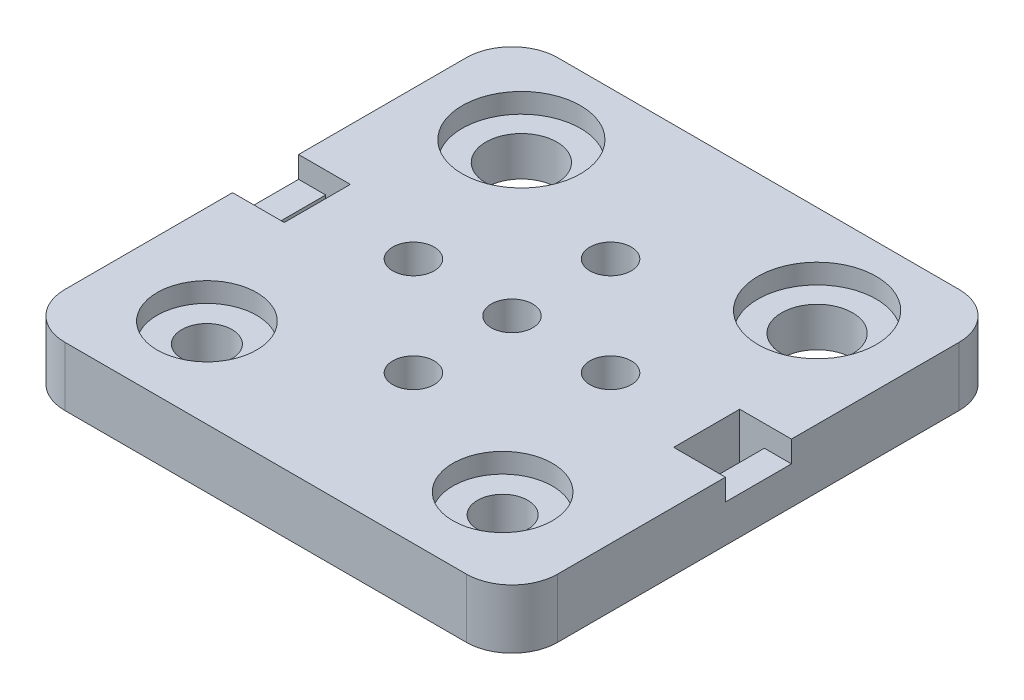
SolidWorks part; units mm, degrees
material "6061-T6 (SS)"
ref_plane "Front Plane" through (0, 0, 0) normal (0, 0, 1) x (1, 0, 0)
ref_plane "Top Plane" through (0, 0, 0) normal (0, 1, 0) x (1, 0, 0)
ref_plane "Right Plane" through (0, 0, 0) normal (1, 0, 0) x (0, 0, -1)
sketch "Sketch1" plane through (0, 0, 0) normal (0, 1, 0) x (1, 0, 0)
  line L0 (-23.7657, 0) -> (0, 0) construction
  line L1 (20.365, -25) -> (-20.365, -25)
  line L2 (25, -20.365) -> (25, 20.365)
  line L3 (20.365, 25) -> (-20.365, 25)
  line L4 (-25, -20.365) -> (-25, 20.365)
  line L5 (25, -25) -> (-25, 25) construction
  line L6 (25, 25) -> (-25, -25) construction
  line L7 (0, 0) -> (0, 28.9978) construction
  arc A0 (-20.365, 25) -> (-25, 20.365) centre (-20.365, 20.365) ccw
  arc A1 (25, 20.365) -> (20.365, 25) centre (20.365, 20.365) ccw
  arc A2 (-20.365, -25) -> (-25, -20.365) centre (-20.365, -20.365) cw
  arc A3 (20.365, -25) -> (25, -20.365) centre (20.365, -20.365) ccw
  circle A4 centre (-15, 15.95) radius 3.6
  circle A16 centre (15, 15.95) radius 3.6
  circle A33 centre (15, -15.95) radius 2.55
  circle A34 centre (-15, -15.95) radius 2.55
  point P0 (0, 0)
  dimension "D2" = 4.635
  dimension "D3" = 30
  dimension "D4" = 7.2
  dimension "D5" = 5.1
  dimension "D1" = 50
  dimension "D10" = 31.9
extrude "Boss-Extrude1" add sketch "Sketch1" along normal blind 6
hole_wizard "M5x0.8 Tapped Hole1" positions "Sketch4" profile "Sketch3" tap size "M5x0.8" standard "ANSI Metric" end condition through all
sketch "Sketch4" plane through (0, 6, 0) normal (0, 1, 0) x (1, 0, 0)
  line L0 (-17.7377, 0) -> (0, 0) construction
  line L1 (0, 0) -> (0, 30.1375) construction
  point P12 (0, 10)
  point P27 (-10, 0)
  point P31 (0, 0)
  point P34 (0, -10)
  point P36 (10, 0)
  dimension "D1" = 20
  dimension "D2" = 20
sketch "Sketch3" plane through (0, 6, -10) normal (1, 0, 0) x (0, 0, 1)
  line L0 (0, 0) -> (0, 6)
  line L1 (0, 6) -> (2.1, 6)
  line L2 (2.1, 6) -> (2.1, 0)
  line L5 (2.1, 0) -> (0, 0)
  line L11 (0, -6.35) -> (0, 107.95) construction
  dimension "Thread Major Dia." = 4.2
  dimension "Thru Tap Drill Depth" = 6
sketch "Sketch2" plane through (0, 6, 0) normal (0, 1, 0) x (1, 0, 0)
  circle A0 centre (-15, 15.95) radius 6
  circle A1 centre (15, 15.95) radius 6
  circle A2 centre (15, -15.95) radius 5.05
  circle A3 centre (-15, -15.95) radius 5.05
  dimension "D1" = 12
  dimension "D2" = 10.1
extrude "Cut-Extrude1" cut sketch "Sketch2" against normal blind 2
sketch "Sketch5" plane through (0, 6, 0) normal (0, 1, 0) x (1, 0, 0)
  line L0 (-25, 20.365) -> (-25, -20.365) construction
  line L1 (-25, 3.35) -> (-19.75, 3.35)
  line L2 (-25, 3.35) -> (-25, -3.35)
  line L3 (-25, -3.35) -> (-19.75, -3.35)
  line L4 (-19.75, 3.35) -> (-19.75, -3.35)
  line L5 (-19.75, 0) -> (0, 0) construction
  line L6 (0, 0) -> (0, 18.5468) construction
  line L7 (19.75, 3.35) -> (19.75, -3.35)
  line L8 (25, -3.35) -> (19.75, -3.35)
  line L9 (25, 3.35) -> (25, -3.35)
  line L10 (25, 3.35) -> (19.75, 3.35)
  dimension "D1" = 6.7
  dimension "D2" = 5.25
extrude "Cut-Extrude2" cut sketch "Sketch5" against normal blind 2.18
sketch "Sketch6" plane through (0, 3.82, 0) normal (0, 1, 0) x (1, 0, 0)
  line L0 (-25, -3.35) -> (-19.75, -3.35) construction
  line L1 (-19.75, 3.35) -> (-22.25, 3.35)
  line L2 (-19.75, 3.35) -> (-19.75, -3.35)
  line L3 (-19.75, -3.35) -> (-22.25, -3.35)
  line L4 (-22.25, 3.35) -> (-22.25, -3.35)
  line L5 (0, 0) -> (0, 14.6011) construction
  line L6 (22.25, 3.35) -> (22.25, -3.35)
  line L7 (19.75, -3.35) -> (22.25, -3.35)
  line L8 (19.75, 3.35) -> (19.75, -3.35)
  line L9 (19.75, 3.35) -> (22.25, 3.35)
  dimension "D1" = 2.5
extrude "Cut-Extrude3" cut sketch "Sketch6" against normal through all
